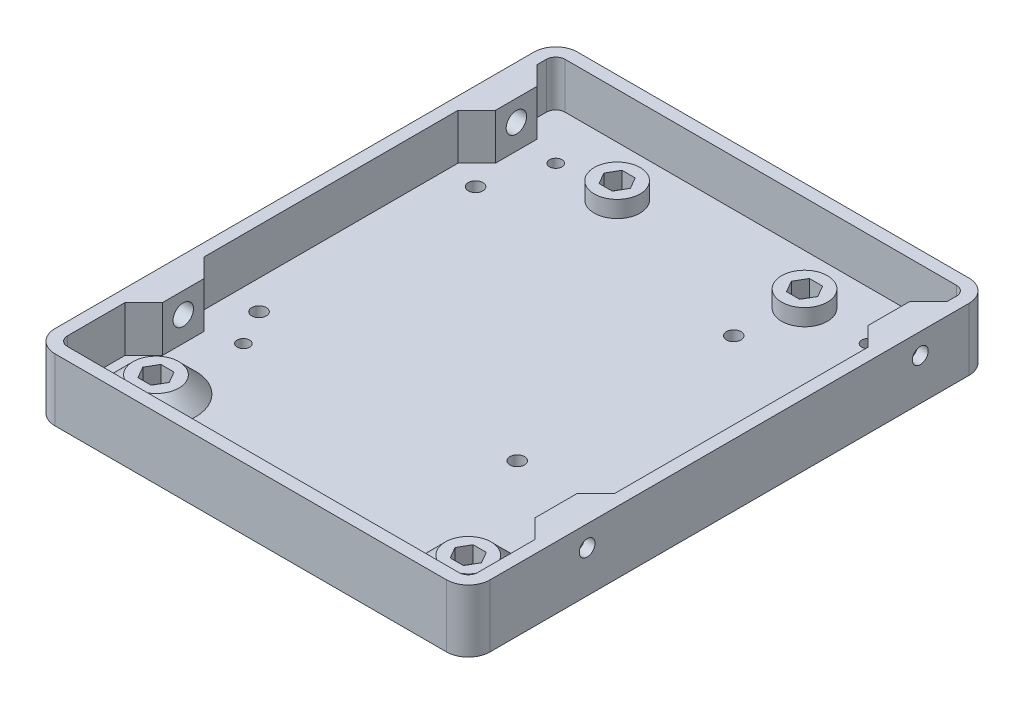
SolidWorks part; units mm, degrees
ref_plane "Front Plane" through (0, 0, 0) normal (0, 0, 1) x (1, 0, 0)
ref_plane "Top Plane" through (0, 0, 0) normal (0, 1, 0) x (1, 0, 0)
ref_plane "Right Plane" through (0, 0, 0) normal (1, 0, 0) x (0, 0, -1)
sketch "Sketch1" plane through (0, 0, 0) normal (0, 1, 0) x (1, 0, 0)
  line L1 (-52.25, 125.5) -> (52.25, 125.5)
  line L2 (-52.25, 125.5) -> (-52.25, 0)
  line L3 (-52.25, 0) -> (52.25, 0)
  line L4 (52.25, 125.5) -> (52.25, 0)
  point P4 (0, 0)
  dimension "D1" = 104.5
  dimension "D2" = 125.5
extrude "Boss-Extrude1" add sketch "Sketch1" along normal blind 4
sketch "Sketch15" plane through (0, 0, 0) normal (0, -1, 0) x (1, 0, 0)
  line L0 (0, -125.5) -> (0, 0) construction
  line L1 (52.25, -125.5) -> (-52.25, -125.5) construction
  line L2 (-52.25, 0) -> (52.25, 0) construction
  circle A0 centre (-22.5, -110.5) radius 10
  circle A1 centre (22.5, -110.5) radius 10
  point P10 (-22.9319, -111.3641)
  dimension "D1" = 20
  dimension "D2" = 45
  dimension "D3" = 15
fillet "Fillet1" radius 5.25 4 edges at (-52.25, 2, 0) (-52.25, 2, -125.5) (52.25, 2, -125.5) (52.25, 2, 0)
ref_plane "Plane1" through (0, 0, -62.75) normal (0, 0, 1) x (1, 0, 0)
sketch "Sketch2" plane through (0, 0, 0) normal (0, -1, 0) x (1, 0, 0)
  line L0 (-52.25, -62.75) -> (0, -62.75) construction
  line L1 (-52.25, -120.25) -> (-52.25, -5.25) construction
  line L2 (0, -62.75) -> (0, 0) construction
  line L4 (-47, 0) -> (47, 0) construction
  circle A0 centre (-37.5, -14.75) radius 5.5
  circle A1 centre (37.5, -14.75) radius 5.5
  circle A2 centre (37.5, -110.75) radius 5.5 construction
  circle A3 centre (-37.5, -110.75) radius 5.5 construction
  circle A4 centre (-22.5, -110.5) radius 5.5
  circle A5 centre (22.5, -110.5) radius 5.5
  dimension "D1" = 11
  dimension "D2" = 14.75
  dimension "D3" = 14.75
  dimension "D4" = 75
  dimension "D5" = 96
sketch "Sketch3" plane through (0, 4, 0) normal (0, 1, 0) x (1, 0, 0)
  line L4 (47, 125.5) -> (-47, 125.5)
  line L5 (-52.25, 120.25) -> (-52.25, 5.25)
  line L6 (-47, 0) -> (47, 0)
  line L7 (52.25, 5.25) -> (52.25, 120.25)
  line L8 (47, 125.5) -> (-47, 125.5)
  line L9 (-52.25, 120.25) -> (-52.25, 5.25)
  line L10 (-47, 0) -> (47, 0)
  line L11 (52.25, 5.25) -> (52.25, 120.25)
  arc A4 (-47, 125.5) -> (-52.25, 120.25) centre (-47, 120.25) ccw
  arc A5 (-52.25, 5.25) -> (-47, 0) centre (-47, 5.25) ccw
  arc A6 (47, 0) -> (52.25, 5.25) centre (47, 5.25) ccw
  arc A7 (52.25, 120.25) -> (47, 125.5) centre (47, 120.25) ccw
  arc A8 (-47, 125.5) -> (-52.25, 120.25) centre (-47, 120.25) ccw
  arc A9 (-52.25, 5.25) -> (-47, 0) centre (-47, 5.25) ccw
  arc A10 (47, 0) -> (52.25, 5.25) centre (47, 5.25) ccw
  arc A11 (52.25, 120.25) -> (47, 125.5) centre (47, 120.25) ccw
  dimension "D1" = 0
extrude "Extrude-Thin1" add sketch "Sketch3" along normal offset from surface (11 mm away) 15 thin up to face at (0, 0, -62.75) thin type one direction reverse wall 3
sketch "Sketch6" plane through (0, 4, 0) normal (0, 1, 0) x (1, 0, 0)
  line L0 (0, 122.5) -> (0, 73.25) construction
  line L1 (0, 62.75) -> (0, 0) construction
  line L2 (0, 73.25) -> (49.25, 73.25) construction
  line L3 (47, 122.5) -> (-47, 122.5) construction
  line L4 (49.25, 5.25) -> (49.25, 120.25) construction
  line L5 (47, 125.5) -> (-47, 125.5) construction
  circle A0 centre (-37.5, 110.75) radius 1.5
  circle A1 centre (37.5, 110.75) radius 1.5
  circle A2 centre (37.5, 35.75) radius 1.5
  circle A3 centre (-37.5, 35.75) radius 1.5
  dimension "D1" = 75
  dimension "D2" = 75
  dimension "D3" = 14.75
  dimension "D4" = 3
extrude "Cut-Extrude2" cut sketch "Sketch6" against normal up to next
sketch "Sketch5" plane through (-52.25, 0, 0) normal (-1, 0, 0) x (0, 0, 1)
  line L0 (-68.55, 0) -> (-68.55, 15) construction
  line L3 (-120.25, 0) -> (-5.25, 0) construction
  line L4 (-120.25, 15) -> (-5.25, 15) construction
  circle A0 centre (-108.55, 10) radius 1.9
  circle A1 centre (-28.55, 10) radius 1.9
  point P8 (-62.75, 0)
  dimension "D1" = 80
  dimension "D2" = 10
  dimension "D3" = 3.8
  dimension "D4" = 5.8
sketch "Sketch8" plane through (-49.25, 0, 0) normal (1, 0, 0) x (0, 0, -1)
  line L0 (120.25, 15) -> (5.25, 15) construction
  line L1 (23.55, 15) -> (33.55, 15)
  line L2 (23.55, 15) -> (23.55, 4)
  line L3 (23.55, 4) -> (33.55, 4)
  line L4 (33.55, 15) -> (33.55, 4)
  line L5 (37.25, 4) -> (34.25, 4) construction
  line L6 (28.55, 10) -> (28.55, 15) construction
  line L7 (68.55, 15) -> (68.55, 42.5997) construction
  line L8 (108.55, 10) -> (108.55, 15) construction
  line L9 (103.55, 15) -> (103.55, 4)
  line L10 (113.55, 4) -> (103.55, 4)
  line L11 (113.55, 15) -> (113.55, 4)
  line L12 (113.55, 15) -> (103.55, 15)
  dimension "D1" = 10
extrude "Boss-Extrude2" add sketch "Sketch8" along normal blind 4.5
mirror "Mirror4" about plane through (0, 0, 0) normal (1, 0, 0) of "Boss-Extrude2"
chamfer "Chamfer2" distance 4.5 angle 45 8 edges at (-49.25, 9.5, -113.55) (-49.25, 9.5, -103.55) (-49.25, 9.5, -33.55) (-49.25, 9.5, -23.55) (49.25, 9.5, -113.55) (49.25, 9.5, -103.55) (49.25, 9.5, -23.55) (49.25, 9.5, -33.55)
extrude "Cut-Extrude3" cut sketch "Sketch5" against normal through all
sketch "Sketch10" plane through (-44.75, 0, 0) normal (1, 0, 0) x (0, 0, -1)
  circle A0 centre (28.55, 10) radius 2.45
  circle A1 centre (108.55, 10) radius 2.45
  dimension "D1" = 4.9
extrude "Cut-Extrude4" cut sketch "Sketch10" against normal blind 5
sketch "Sketch12" plane through (0, 4, 0) normal (0, 1, 0) x (1, 0, 0)
  line L0 (0, 62.75) -> (0, 0) construction
  line L1 (-34.3246, 14.75) -> (-35.9123, 17.5)
  line L2 (-35.9123, 17.5) -> (-39.0877, 17.5)
  line L3 (-39.0877, 17.5) -> (-40.6754, 14.75)
  line L4 (-40.6754, 14.75) -> (-39.0877, 12)
  line L5 (-39.0877, 12) -> (-35.9123, 12)
  line L6 (-35.9123, 12) -> (-34.3246, 14.75)
  line L7 (35.9123, 12) -> (34.3246, 14.75)
  line L8 (39.0877, 12) -> (35.9123, 12)
  line L9 (40.6754, 14.75) -> (39.0877, 12)
  line L10 (39.0877, 17.5) -> (40.6754, 14.75)
  line L11 (35.9123, 17.5) -> (39.0877, 17.5)
  line L12 (34.3246, 14.75) -> (35.9123, 17.5)
  line L13 (25.6754, 110.5) -> (24.0877, 107.75)
  line L14 (-19.3246, 110.5) -> (-20.9123, 113.25)
  line L15 (-20.9123, 113.25) -> (-24.0877, 113.25)
  line L16 (-24.0877, 113.25) -> (-25.6754, 110.5)
  line L17 (-25.6754, 110.5) -> (-24.0877, 107.75)
  line L18 (-24.0877, 107.75) -> (-20.9123, 107.75)
  line L19 (-20.9123, 107.75) -> (-19.3246, 110.5)
  line L20 (24.0877, 113.25) -> (25.6754, 110.5)
  line L21 (20.9123, 113.25) -> (24.0877, 113.25)
  line L22 (19.3246, 110.5) -> (20.9123, 113.25)
  line L23 (20.9123, 107.75) -> (19.3246, 110.5)
  line L24 (24.0877, 107.75) -> (20.9123, 107.75)
  circle A0 centre (-37.5, 14.75) radius 2.75 construction
  circle A1 centre (-22.5, 110.5) radius 2.75 construction
  dimension "D1" = 5.5
extrude "Boss-Extrude3" add sketch "Sketch2" against normal offset from surface (8 mm away) 4 up to face at (0, 4, -66.6167) offset beyond the face yes
extrude "Cut-Extrude5" cut sketch "Sketch12" along normal through all
sketch "Sketch13" plane through (0, 4, 0) normal (0, 1, 0) x (1, 0, 0)
  circle A0 centre (37.5, 14.75) radius 1.75
  circle A1 centre (-37.5, 14.75) radius 1.75
  circle A2 centre (-22.5, 110.5) radius 1.75
  circle A3 centre (22.5, 110.5) radius 1.75
  dimension "D1" = 3.5
extrude "Cut-Extrude6" cut sketch "Sketch13" against normal through all
chamfer "Chamfer3" distance 4 angle 45 2 edges at (37.5, 4, -9.25) (-37.5, 4, -9.25)
sketch "Sketch14" plane through (0, 4, 0) normal (0, 1, 0) x (1, 0, 0)
  line L0 (-49.25, 99.05) -> (-49.25, 38.05) construction
  line L1 (-42.25, 96.25) -> (19.75, 96.25) construction
  line L2 (-42.25, 96.25) -> (-42.25, 44.25) construction
  line L3 (-42.25, 44.25) -> (19.75, 44.25) construction
  line L4 (19.75, 96.25) -> (19.75, 44.25) construction
  line L5 (-37.5, 110.75) -> (-37.5, 35.75) construction
  line L7 (-37.5, 73.25) -> (-42.25, 70.25) construction
  circle A0 centre (-42.25, 96.25) radius 1.75
  circle A1 centre (19.75, 96.25) radius 1.75
  circle A2 centre (19.75, 44.25) radius 1.75
  circle A3 centre (-42.25, 44.25) radius 1.75
  dimension "D3" = 3.5
  dimension "D1" = 52
  dimension "D2" = 62
  dimension "D4" = 7
  dimension "D5" = 3
extrude "Cut-Extrude7" cut sketch "Sketch14" against normal through all
mirror "Mirror5" about plane through (0, 0, 0) normal (1, 0, 0) of "Cut-Extrude4"
